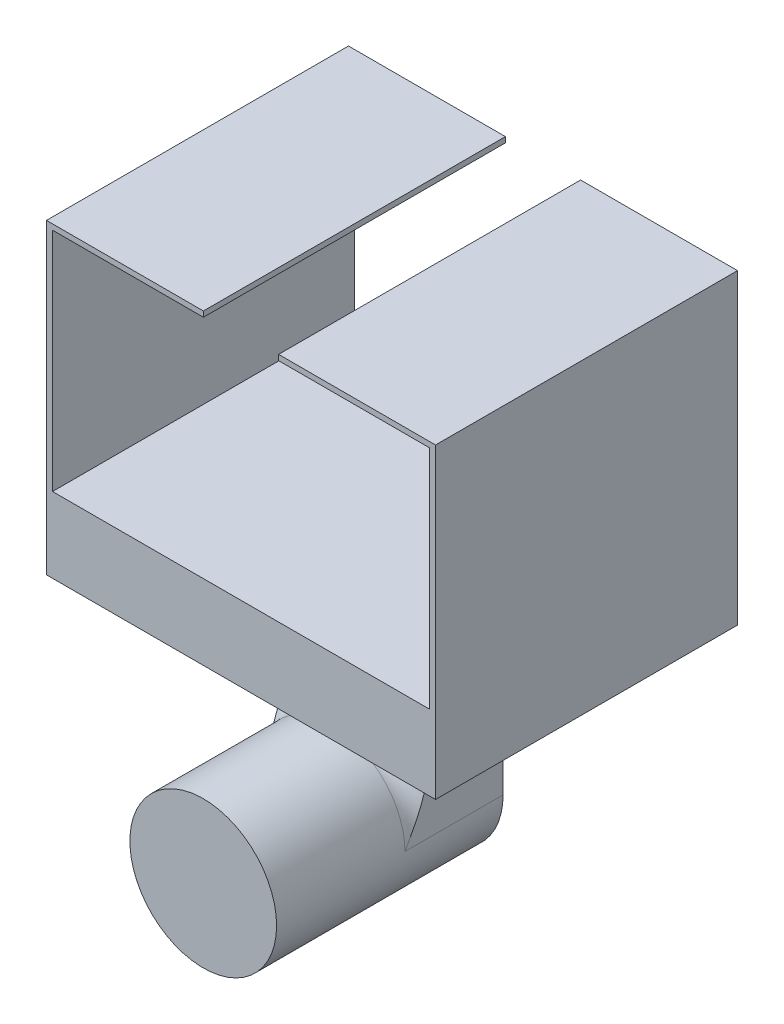
SolidWorks part; units mm, degrees
material "6061-T6 (SS)"
ref_plane "Front Plane" through (0, 0, 0) normal (0, 0, 1) x (1, 0, 0)
ref_plane "Top Plane" through (0, 0, 0) normal (0, 1, 0) x (1, 0, 0)
ref_plane "Right Plane" through (0, 0, 0) normal (1, 0, 0) x (0, 0, -1)
sketch "Sketch1" plane through (0, 0, 0) normal (0, 0, 1) x (1, 0, 0)
  circle A0 centre (0, 0) radius 12.3372
  dimension "D1" = 24.6745
extrude "Boss-Extrude1" add sketch "Sketch1" against normal blind 38.1
sketch "Sketch2" plane through (0, 0, -38.1) normal (0, 0, -1) x (-1, 0, 0)
  line L0 (-12.3372, 0) -> (12.3372, 0)
  line L1 (12.3372, 0) -> (12.3372, 25.4)
  line L2 (12.3372, 25.4) -> (-12.3372, 25.4)
  line L3 (-12.3372, 0) -> (-12.3372, 25.4)
  circle A0 centre (0, 0) radius 12.3372 construction
extrude "Boss-Extrude2" add sketch "Sketch2" against normal blind 12.7
sketch "Sketch6" plane through (0, 25.4, 0) normal (0, 1, 0) x (1, 0, 0)
  line L0 (-12.3372, 31.75) -> (12.3372, 31.75) construction
  line L1 (-12.3372, 25.4) -> (-12.3372, 38.1) construction
  line L2 (12.3372, 25.4) -> (12.3372, 38.1) construction
  line L3 (0, 31.75) -> (0, 38.1) construction
  line L6 (-12.3372, 38.1) -> (12.3372, 38.1) construction
  line L7 (-32.721, 57.15) -> (32.721, 57.15)
  line L8 (-32.721, 57.15) -> (-32.721, 6.35)
  line L9 (-32.721, 6.35) -> (32.721, 6.35)
  line L10 (32.721, 57.15) -> (32.721, 6.35)
  line L11 (0, 38.1) -> (0, 25.4) construction
  line L12 (-12.3372, 25.4) -> (12.3372, 25.4) construction
  dimension "D2" = 65.4419
extrude "Boss-Extrude3" add sketch "Sketch6" along normal blind 51.6394
sketch "Sketch7" plane through (0, 0, -6.35) normal (0, 0, 1) x (1, 0, 0)
  line L0 (-12.3372, 25.4) -> (12.3372, 25.4) construction
  line L1 (-31.7043, 38.0492) -> (31.7043, 38.0492)
  line L2 (-31.7043, 38.0492) -> (-31.7043, 76.1238)
  line L3 (-31.7043, 76.1238) -> (31.7043, 76.1238)
  line L4 (31.7043, 38.0492) -> (31.7043, 76.1238)
  line L5 (0, 77.0394) -> (0, 25.4) construction
  line L6 (-32.721, 77.0394) -> (32.721, 77.0394) construction
  line L7 (-32.721, 25.4) -> (32.721, 25.4) construction
  line L8 (-32.721, 51.2197) -> (32.721, 51.2197) construction
  line L9 (-32.721, 77.0394) -> (-32.721, 25.4) construction
  line L10 (32.721, 77.0394) -> (32.721, 25.4) construction
  dimension "D1" = 12.6492
  dimension "D2" = 63.4086
  dimension "D3" = 38.0746
extrude "Cut-Extrude1" cut sketch "Sketch7" against normal through all
sketch "Sketch8" plane through (0, 0, -6.35) normal (0, 0, 1) x (1, 0, 0)
  line L0 (31.7043, 76.1238) -> (-31.7043, 76.1238) construction
  line L1 (-6.3246, 76.1238) -> (6.3246, 76.1238)
  line L2 (-6.3246, 76.1238) -> (-6.3246, 77.0394)
  line L3 (-6.3246, 77.0394) -> (6.3246, 77.0394)
  line L4 (6.3246, 76.1238) -> (6.3246, 77.0394)
  line L5 (-32.721, 77.0394) -> (32.721, 77.0394) construction
  line L6 (0, 38.0492) -> (0, 76.1238) construction
  line L7 (-31.7043, 38.0492) -> (31.7043, 38.0492) construction
  dimension "D2" = 12.6492
extrude "Cut-Extrude2" cut sketch "Sketch8" against normal through all
fillet "Fillet1" radius 3.81 1 edges at (0, 12.3372, -25.4)
fillet "Fillet2" radius 6.35 1 edges at (0, 25.4, -25.4)
equation "\"F\"= 600'applied force (lbf)"
equation "\"SF\"= 4'Safety Factor"
equation "\"Sy\"= 40000'Yield Strength (PSI)"
equation "\"La\" = 1.5in'Feature A length"
equation "\"Ma\"= \"F\" * \"La\"'lbf in"
equation "\"Za\"= \"SF\" * \"Ma\" / \"Sy\"'Section Modulus (in^3)"
equation "\"ra\"= ( 4 * \"Za\" / pi ) ^ ( 1 / 3 )'RADIUS A"
equation "\"D\"= \"ra\" * 2'DIAMETER A"
equation "\"P_B\"= \"F\" * 2' FEATURE B AXIAL LOAD LBF"
equation "\"ALLOWSTRESS\"= \"Sy\" / \"SF\"'ALLOWABLE NORMAL STRESS"
equation "\"A_B\"= \"P_B\" / \"ALLOWSTRESS\"'FEATURE B REQUIRED AREA IN^2"
equation "\"T_B\" = 0.5in'FEATURE B REQUIRED THICKNESS"
equation "\"L_B\"= 1in'LENGTH OF B"
equation "\"L_C\"= \"A_FIT\" + \"B_FIT\" * 2'FEATURE C SPAN"
equation "\"B_C\"= 2in'BRACKET DEPTH"
equation "\"M_C\"= \"P_B\" * \"L_C\" / 4'MAX BENDING MOMENT"
equation "\"Z_C\"= \"M_C\" / \"ALLOWSTRESS\"'REQUIRED SECTION MODULUS IN^3"
equation "\"H_C\"= sqr ( 6 * \"Z_C\" / \"B_C\" )'required c thickness"
equation "\"P_D\"= \"F\"'FEATURE D AXIAL LOAD LBF"
equation "\"A_D\"= \"P_D\" / \"ALLOWSTRESS\"'FEATURE D REQUIRED AREA "
equation "\"P_E\"= \"F\"'E AXIAL LOAD LBF"
equation "\"A_E\"= \"P_E\" / \"ALLOWSTRESS\"'FEATURE E REQUIRED AREA"
equation "\"A_FIT\"= 0.498IN'T BEAM INTERFACE DIM A"
equation "\"B_FIT\"= 0.9992in'T BEAM INTERFACE DIM B"
equation "\"C_FIT\"= 1.499in'T BEAM INTERFACE DIM C"
equation "\"T_D\"= \"A_D\" / \"C_FIT\"'FEATURE D REQUIRED THIVKNESS"
equation "\"T_E\"= \"A_E\" / \"B_FIT\"'FEATURE E REQUIRED THICKNESS"
equation "\"OVERALLWIDTH\"= \"L_C\" + \"T_D\" * 2'SLECTED OVERALL BRACKET WIDTH"
equation "\"OVERALLHEIGHT\"= \"H_C\" + \"T_E\" + \"C_FIT\""
equation "\"D1@Boss-Extrude2\"= \"T_B\""
equation "\"D1@Sketch1\"= \"D\""
equation "\"D1@Boss-Extrude1\"= \"La\""
equation "\"D1@Sketch2\"= \"L_B\""
equation "\"D1@Sketch6\"= \"B_C\""
equation "\"D2@Sketch6\"= \"OVERALLWIDTH\""
equation "\"D1@Boss-Extrude3\"= \"OVERALLHEIGHT\""
equation "\"D1@Sketch7\"= \"A_FIT\""
equation "\"D2@Sketch7\"= \"L_C\""
equation "\"D3@Sketch7\"= \"C_FIT\""
